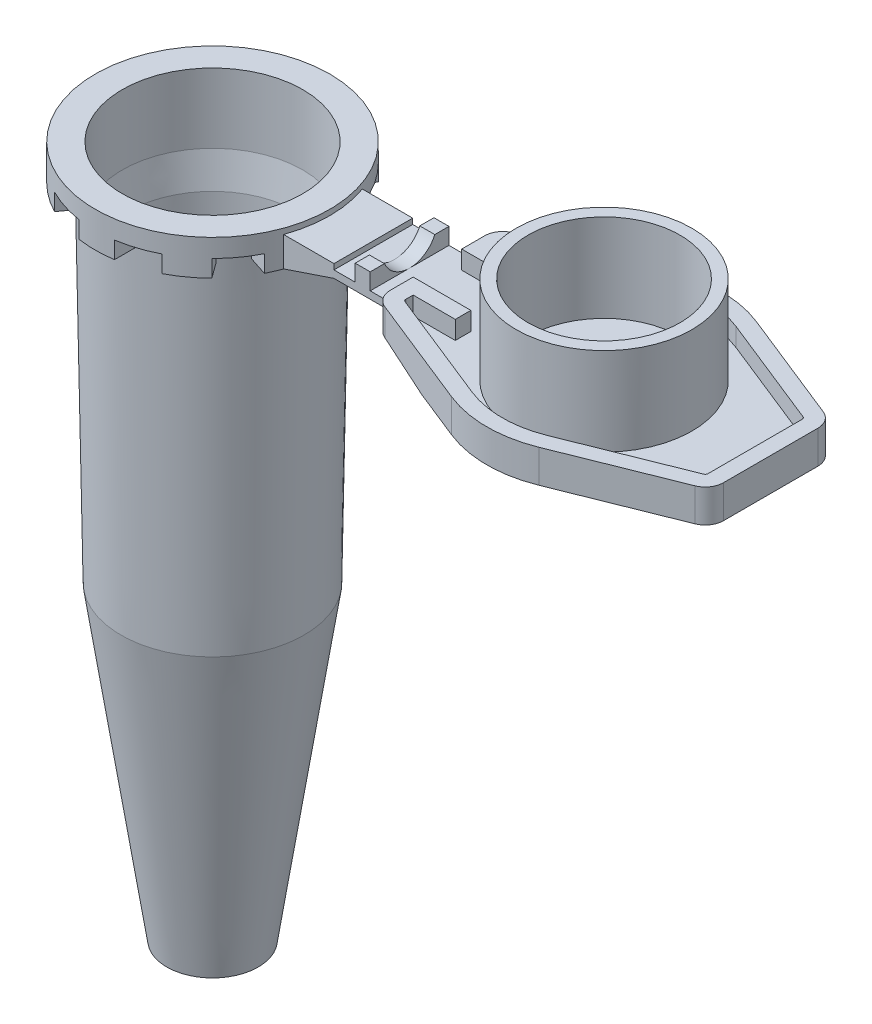
SolidWorks part; units mm, degrees
ref_plane "Front Plane" through (0, 0, 0) normal (0, 0, 1) x (1, 0, 0)
ref_plane "Top Plane" through (0, 0, 0) normal (0, 1, 0) x (1, 0, 0)
ref_plane "Right Plane" through (0, 0, 0) normal (1, 0, 0) x (0, 0, -1)
sketch "Sketch1" plane through (0, 0, 0) normal (0, 0, 1) x (1, 0, 0)
  line L0 (0, 0) -> (0, 43.428) construction
  line L1 (0, 38.64) -> (-6.405, 38.64)
  line L2 (-6.405, 38.64) -> (-6.405, 37.64)
  line L3 (-6.405, 37.64) -> (-5.325, 37.64)
  line L4 (-5.325, 37.64) -> (-5, 17.8)
  line L5 (-5, 17.8) -> (-2.5, 0.85)
  line L7 (0, 38.64) -> (0, 0)
  line L8 (-18.3321, 0.85) -> (18.9529, 0.85) construction
  arc A0 (-2.5, 0.85) -> (0, 0) centre (0, 4.1015) ccw
  point P12 (-2.5, 0.85)
  point P13 (2.5, 0.85)
  dimension "D7" = 5
  dimension "D1" = 38.64
  dimension "D2" = 12.81
  dimension "D3" = 17.8
  dimension "D4" = 10
  dimension "D5" = 10.65
  dimension "D6" = 1
  dimension "D10" = 1.7
revolve "Revolve1" add sketch "Sketch1" angle 360 about L0
sketch "Sketch2" plane through (0, 0, 0) normal (0, 0, 1) x (1, 0, 0)
  line L0 (0, 0.8) -> (0, 41.0311) construction
  line L2 (6.405, 38.64) -> (-6.405, 38.64) construction
  line L3 (-4.6, 33.04) -> (-4.25, 18.44)
  line L5 (0, 38.64) -> (0, 0) construction
  line L7 (-4.25, 18.44) -> (-1.9986, 2.5356)
  line L10 (0, 0.8) -> (4.8244, 0.8) construction
  line L16 (-4.93, 38.64) -> (-4.93, 34.84)
  line L17 (0, 38.64) -> (-6.405, 38.64) construction
  line L19 (0, 0.8) -> (0, 38.64)
  line L20 (0, 38.64) -> (-4.93, 38.64)
  line L21 (-4.6, 33.04) -> (-4.93, 34.84)
  arc A6 (-1.9986, 2.5356) -> (0, 0.8) centre (0, 2.8185) ccw
  point P0 (-3.5705, 13.64)
  point P2 (-4, 16.674)
  point P4 (-1.901, 2.14)
  point P12 (-4.8789, 44.6737)
  dimension "D1" = 9.86
  dimension "D2" = 9.2
  dimension "D3" = 8.5
  dimension "D4" = 0.8
  dimension "D5" = 25
  dimension "D6" = 9.7578
  dimension "D7" = 8
  dimension "D8" = 3.8
  dimension "D9" = 5.6
  dimension "D10" = 20.2
  dimension "D11" = 21.966
  dimension "D12" = 7.141
  dimension "D13" = 36.1044
  dimension "D14" = 36.5
  dimension "D15" = 3.8021
other "AlignGroup1"
revolve "Cut-Revolve1" cut sketch "Sketch2" angle 360 about L0
sketch "Sketch3" plane through (0, 37.64, 0) normal (0, -1, 0) x (1, 0, 0)
  line L0 (-0.975, 6.3304) -> (-0.975, 5.235)
  line L1 (0, 0) -> (0, 7.664) construction
  line L2 (0.975, 6.3304) -> (0.975, 5.235)
  circle A0 centre (0, 0) radius 5.325 construction
  arc A1 (0.975, 5.235) -> (-0.975, 5.235) centre (0, 0) ccw
  circle A2 centre (0, 0) radius 6.405 construction
  arc A3 (0.975, 6.3304) -> (-0.975, 6.3304) centre (0, 0) ccw
  dimension "D1" = 1.95
extrude "Boss-Extrude1" add sketch "Sketch3" along normal offset from surface (0.93 mm away) 1.93 up to face at (0, 38.64, -4.93)
pattern_circular "CirPattern1" count 10 over 360 about axis through (0, 38.64, 0) along (0, -1, 0) of "Boss-Extrude1"
sketch "Sketch5" plane through (0, 36.71, 0) normal (0, -1, 0) x (1, 0, 0)
  line L0 (-6.1167, 1.9) -> (-5.0895, 1.5662)
  line L1 (-6.1167, -1.9) -> (-5.0895, -1.5662)
  line L2 (0, 0) -> (-8.3672, 0) construction
  line L3 (-6.3218, 1.0289) -> (-5.2801, 0.6904) construction
  arc A0 (-5.7192, 2.8835) -> (-6.3218, 1.0289) centre (0, 0) ccw construction
  arc A1 (-4.6775, 2.545) -> (-5.2801, 0.6904) centre (0, 0) ccw construction
  arc A2 (-6.3218, -1.0289) -> (-5.7192, -2.8835) centre (0, 0) ccw construction
  arc A3 (-5.2801, -0.6904) -> (-4.6775, -2.545) centre (0, 0) ccw construction
  arc A4 (-5.0895, 1.5662) -> (-5.0895, -1.5662) centre (0, 0) ccw
  arc A5 (-6.1167, 1.9) -> (-6.1167, -1.9) centre (0, 0) ccw
  dimension "D1" = 3.8
extrude "Cut-Extrude1" cut sketch "Sketch5" against normal up to surface (0.93 mm away) up to face at (-5.833, 37.64, 0)
sketch "Sketch6" plane through (0, 37.64, 0) normal (0, -1, 0) x (1, 0, 0)
  line L0 (0, 0) -> (15.5128, 0) construction
  line L1 (6.0334, 2.15) -> (12.2834, 2.15)
  line L3 (6.0334, -2.15) -> (12.2834, -2.15)
  line L4 (12.2834, 2.15) -> (12.2834, -2.15)
  circle A0 centre (0, 0) radius 6.405 construction
  arc A1 (6.0334, -2.15) -> (6.0334, 2.15) centre (0, 0) ccw
  dimension "D1" = 4.3
  dimension "D2" = 6.25
extrude "Boss-Extrude2" add sketch "Sketch6" against normal blind 0.4
sketch "Sketch7" plane through (0, 0, -2.15) normal (0, 0, -1) x (-1, 0, 0)
  line L0 (-6.0334, 38.04) -> (-6.0334, 38.34)
  line L1 (-6.0334, 38.34) -> (-8.7834, 38.34)
  line L2 (-8.7834, 38.34) -> (-8.7834, 38.04)
  line L3 (-6.0334, 38.04) -> (-12.2834, 38.04) construction
  line L4 (-8.7834, 38.04) -> (-6.0334, 38.04)
  dimension "D1" = 2.75
  dimension "D2" = 0.3
extrude "Boss-Extrude3" add sketch "Sketch7" against normal up to surface (4.3 mm away) up to face at (9.1584, 37.84, 2.15)
sketch "Sketch8" plane through (0, 0, -2.15) normal (0, 0, -1) x (-1, 0, 0)
  line L0 (-6.0334, 37.64) -> (-6.0205, 36.71)
  line L1 (-6.3218, 36.71) -> (-5.7192, 36.71) construction
  line L2 (-6.0205, 36.71) -> (-8.7834, 37.64)
  line L3 (-8.7834, 38.34) -> (-8.7834, 38.04) construction
  line L4 (-6.0334, 37.64) -> (-12.2834, 37.64) construction
  line L5 (-8.7834, 37.64) -> (-6.0334, 37.64)
extrude "Boss-Extrude4" add sketch "Sketch8" against normal blind 0.8
mirror "Mirror1" about plane through (0, 0, 0) normal (0, 0, 1) of "Boss-Extrude4"
sketch "Sketch9" plane through (0, 0, -2.15) normal (0, 0, -1) x (-1, 0, 0)
  line L0 (-8.7834, 38.04) -> (-12.2834, 38.04) construction
  line L1 (-9.9434, 38.04) -> (-10.7634, 38.04)
  line L2 (-9.9434, 38.04) -> (-9.9434, 38.94)
  line L3 (-9.9434, 38.94) -> (-10.7634, 38.94)
  line L4 (-10.7634, 38.04) -> (-10.7634, 38.94)
  line L5 (-8.7834, 38.34) -> (-8.7834, 38.04) construction
  line L6 (-8.7834, 37.64) -> (-12.2834, 37.64) construction
  dimension "D1" = 1.16
  dimension "D2" = 0.82
  dimension "D3" = 1.3
extrude "Boss-Extrude5" add sketch "Sketch9" against normal up to surface (4.3 mm away) up to face at (8.9977, 37.822, 2.15)
sketch "Sketch10" plane through (10.7634, 0, 0) normal (1, 0, 0) x (0, 0, -1)
  line L0 (-2.15, 38.04) -> (2.15, 38.04) construction
  line L1 (0, 38.94) -> (0, 42.66) construction
  line L2 (-2.15, 38.94) -> (2.15, 38.94) construction
  circle A0 centre (0, 39.54) radius 1.5
  dimension "D1" = 3
extrude "Cut-Extrude2" cut sketch "Sketch10" against normal up to surface (0.82 mm away) up to face at (9.9434, 38.49, 0)
sketch "Sketch11" plane through (0, 38.04, 0) normal (0, 1, 0) x (1, 0, 0)
  line L0 (12.2834, 0) -> (30.4834, 0) construction
  line L1 (12.2834, 2.15) -> (12.2834, -2.15) construction
  line L2 (21.3834, 6.4) -> (21.3834, -6.4) construction
  line L3 (12.2834, 3.25) -> (12.2834, -3.25)
  line L4 (12.2834, -3.25) -> (19.0042, -5.9413)
  line L5 (12.2834, 3.25) -> (19.0042, 5.9413)
  line L6 (30.4834, 3.25) -> (23.7626, 5.9413)
  line L7 (30.4834, -3.25) -> (23.7626, -5.9413)
  line L8 (30.4834, 3.25) -> (30.4834, -3.25)
  arc A0 (19.0042, -5.9413) -> (23.7626, -5.9413) centre (21.3834, 0) ccw
  arc A1 (23.7626, 5.9413) -> (19.0042, 5.9413) centre (21.3834, 0) ccw
  point P7 (21.3834, 0)
  point P10 (21.3834, 0)
  dimension "D1" = 18.2
  dimension "D2" = 12.8
  dimension "D3" = 6.5
extrude "Boss-Extrude6" add sketch "Sketch11" against normal blind 0.8
sketch "Sketch12" plane through (0, 0, 0) normal (0, 0, 1) x (1, 0, 0)
  line L0 (12.2834, 37.64) -> (16.2834, 37.24)
  line L1 (12.2834, 37.24) -> (19.0042, 37.24) construction
  line L2 (12.2834, 37.64) -> (12.2834, 37.24)
  line L3 (12.2834, 37.24) -> (16.2834, 37.24)
  dimension "D1" = 4
extrude "Cut-Extrude3" cut sketch "Sketch12" against normal through all and the other way through all
fillet "Fillet1" radius 1 4 edges at (30.4834, 37.64, -3.25) (30.4834, 37.64, 3.25) (12.2834, 37.84, -3.25) (12.2834, 37.84, 3.25)
sketch "Sketch13" plane through (0, 38.04, 0) normal (0, 1, 0) x (1, 0, 0)
  circle A0 centre (21.3834, 0) radius 4.8
  circle A1 centre (21.3834, 0) radius 4.15
  dimension "D1" = 9.6
  dimension "D2" = 8.3
extrude "Boss-Extrude7" add sketch "Sketch13" along normal blind 4.8
sketch "Sketch14" plane through (0, 38.04, 0) normal (0, 1, 0) x (1, 0, 0)
  line L0 (12.2834, 2.5732) -> (12.2834, 2.15) construction
  line L1 (19.0042, 5.9413) -> (12.9116, 3.5016) construction
  line L2 (29.8551, 3.5016) -> (23.7626, 5.9413) construction
  line L3 (30.4834, -2.5732) -> (30.4834, 2.5732) construction
  line L4 (23.7626, -5.9413) -> (29.8551, -3.5016) construction
  line L5 (12.2834, -2.15) -> (12.2834, -2.5732) construction
  line L6 (12.9116, -3.5016) -> (19.0042, -5.9413) construction
  line L7 (12.2834, 2.5732) -> (12.2834, 2.15)
  line L8 (19.0042, 5.9413) -> (12.9116, 3.5016)
  line L9 (29.8551, 3.5016) -> (23.7626, 5.9413)
  line L10 (30.4834, -2.5732) -> (30.4834, 2.5732)
  line L11 (23.7626, -5.9413) -> (29.8551, -3.5016)
  line L12 (12.2834, -2.15) -> (12.2834, -2.5732)
  line L13 (12.9116, -3.5016) -> (19.0042, -5.9413)
  line L14 (12.2834, -2.15) -> (12.2834, -1.325)
  line L15 (12.2834, -1.325) -> (15.4334, -1.325)
  line L16 (21.3834, 0) -> (7.7654, 0) construction
  line L17 (12.2834, 1.325) -> (15.4334, 1.325)
  line L18 (12.2834, 2.15) -> (12.2834, 1.325)
  line L19 (13.1334, 2.175) -> (15.4334, 2.175)
  line L20 (13.1334, 2.175) -> (13.1334, 2.175)
  line L21 (13.1334, 2.5732) -> (13.1334, 2.175)
  line L22 (19.3202, 5.1522) -> (13.2276, 2.7125)
  line L23 (29.5391, 2.7125) -> (23.4466, 5.1522)
  line L24 (29.6334, -2.5732) -> (29.6334, 2.5732)
  line L25 (23.4466, -5.1522) -> (29.5391, -2.7125)
  line L26 (13.2276, -2.7125) -> (19.3202, -5.1522)
  line L27 (13.1334, -2.175) -> (13.1334, -2.5732)
  line L28 (13.1334, -2.175) -> (13.1334, -2.175)
  line L29 (13.1334, -2.175) -> (15.4334, -2.175)
  line L30 (15.4334, -2.175) -> (15.4334, -1.325)
  line L31 (15.4334, 1.325) -> (15.4334, 2.175)
  arc A0 (12.9116, 3.5016) -> (12.2834, 2.5732) centre (13.2834, 2.5732) ccw construction
  arc A1 (23.7626, 5.9413) -> (19.0042, 5.9413) centre (21.3834, 0) ccw construction
  arc A2 (30.4834, 2.5732) -> (29.8551, 3.5016) centre (29.4834, 2.5732) ccw construction
  arc A3 (29.8551, -3.5016) -> (30.4834, -2.5732) centre (29.4834, -2.5732) ccw construction
  arc A4 (19.0042, -5.9413) -> (23.7626, -5.9413) centre (21.3834, 0) ccw construction
  arc A5 (12.2834, -2.5732) -> (12.9116, -3.5016) centre (13.2834, -2.5732) ccw construction
  arc A6 (12.9116, 3.5016) -> (12.2834, 2.5732) centre (13.2834, 2.5732) ccw
  arc A7 (23.7626, 5.9413) -> (19.0042, 5.9413) centre (21.3834, 0) ccw
  arc A8 (30.4834, 2.5732) -> (29.8551, 3.5016) centre (29.4834, 2.5732) ccw
  arc A9 (29.8551, -3.5016) -> (30.4834, -2.5732) centre (29.4834, -2.5732) ccw
  arc A10 (19.0042, -5.9413) -> (23.7626, -5.9413) centre (21.3834, 0) ccw
  arc A11 (12.2834, -2.5732) -> (12.9116, -3.5016) centre (13.2834, -2.5732) ccw
  arc A12 (13.2276, 2.7125) -> (13.1334, 2.5732) centre (13.2834, 2.5732) ccw
  arc A13 (23.4466, 5.1522) -> (19.3202, 5.1522) centre (21.3834, 0) ccw
  arc A14 (29.6334, 2.5732) -> (29.5391, 2.7125) centre (29.4834, 2.5732) ccw
  arc A15 (29.5391, -2.7125) -> (29.6334, -2.5732) centre (29.4834, -2.5732) ccw
  arc A16 (19.3202, -5.1522) -> (23.4466, -5.1522) centre (21.3834, 0) ccw
  arc A17 (13.1334, -2.5732) -> (13.2276, -2.7125) centre (13.2834, -2.5732) ccw
  point P24 (13.8584, 1.325)
  dimension "D1" = 2.65
  dimension "D2" = 3.15
  dimension "D3" = 0.85
extrude "Boss-Extrude8" add sketch "Sketch14" along normal blind 1
ref_plane "Lid Closure Plane" through (0, 35.04, 0) normal (0, 1, 0) x (1, 0, 0)
